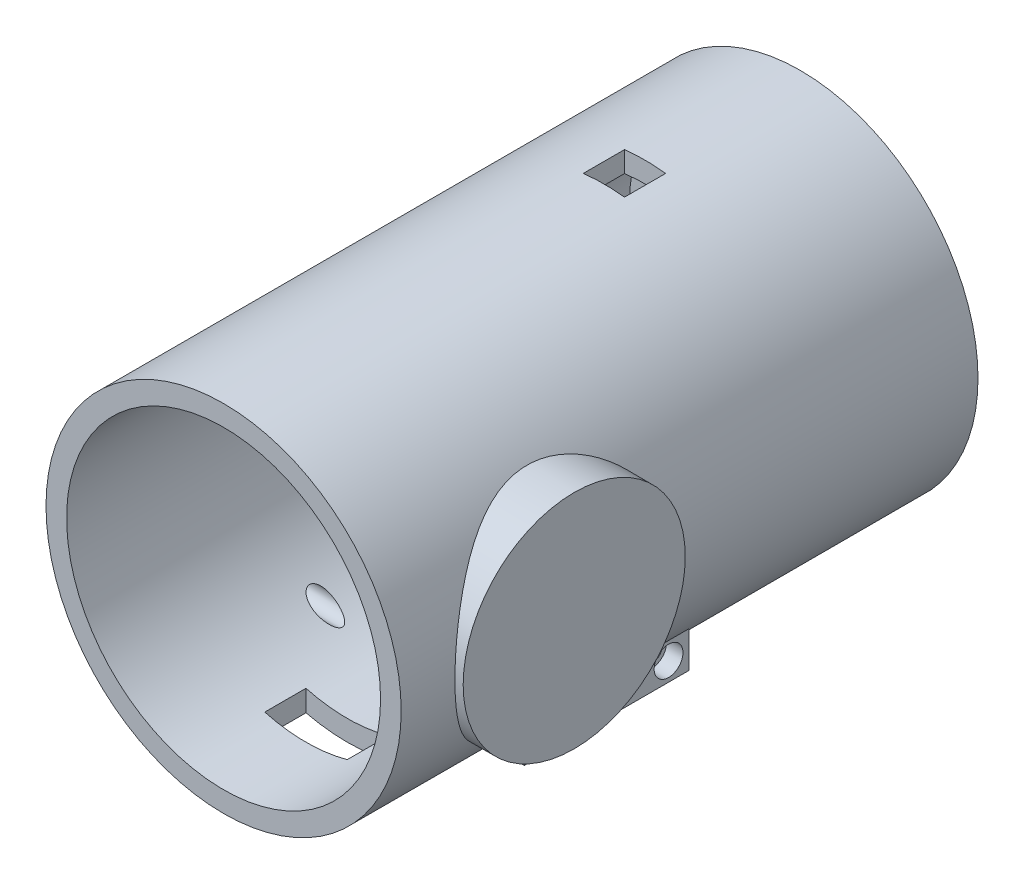
SolidWorks part; units mm, degrees
other "Markup1"
sketch "Sketch14" plane through (-43.1, 43.1, 140) normal (-0.1765, 0.0048, 0.9843) x (0.9842, -0.0149, 0.1765)
other "Markup2"
sketch "Sketch23" plane through (45.1, -43.1, 140) normal (0.9491, -0.0629, 0.3087) x (0.311, 0.031, -0.9499)
ref_plane "Front Plane" through (0, 0, 0) normal (0, 0, 1) x (1, 0, 0)
ref_plane "Top Plane" through (0, 0, 0) normal (0, 1, 0) x (1, 0, 0)
ref_plane "Right Plane" through (0, 0, 0) normal (1, 0, 0) x (0, 0, -1)
sketch "Sketch1" plane through (0, 0, 0) normal (0, 0, 1) x (1, 0, 0)
  circle A1 centre (0, 0) radius 43.1
  dimension "D1" = 86.2
extrude "Main Body" add sketch "Sketch1" along normal blind 140
ref_plane "Plane1" through (0, 43.1, 0) normal (0, 1, 0) x (1, 0, 0)
sketch "Sketch6" plane through (0, 43.1, 0) normal (0, 1, 0) x (1, 0, 0)
  line L2 (-5, -47.7) -> (5, -47.7)
  line L3 (-5, -47.7) -> (-5, -37.7)
  line L4 (-5, -37.7) -> (5, -37.7)
  line L5 (5, -47.7) -> (5, -37.7)
  line L6 (-5, -47.7) -> (5, -37.7) construction
  line L7 (-5, -37.7) -> (5, -47.7) construction
  point P2 (0, -42.7)
  dimension "D2" = 10
  dimension "D1" = 42.7
  dimension "D3" = 10
extrude "Cut-Extrude3" cut sketch "Sketch6" against normal through all
ref_plane "Plane2" through (45.1, 0, 0) normal (1, 0, 0) x (0, 0, -1)
sketch "Sketch8" plane through (45.1, 0, 0) normal (1, 0, 0) x (0, 0, -1)
  circle A0 centre (-100, 0) radius 26.95
  dimension "D1" = 53.9
  dimension "D2" = 100
extrude "Boss-Extrude2" add sketch "Sketch8" against normal blind 20
mirror "Mirror1" [suppressed] about plane through (0, 0, 0) normal (1, 0, 0)
sketch "Sketch5" plane through (0, 0, 140) normal (0, 0, 1) x (1, 0, 0)
  circle A0 centre (0, 0) radius 31.75
  dimension "D1" = 63.5
extrude "Hole 1" cut sketch "Sketch5" against normal through all
sketch "Sketch10" plane through (0, 0, 0) normal (0, 1, 0) x (1, 0, 0)
  line L0 (43.1, 0) -> (-43.1, 0) construction
  line L1 (-10, -120) -> (10, -120)
  line L2 (-10, -120) -> (-10, -110)
  line L3 (-10, -110) -> (10, -110)
  line L4 (10, -120) -> (10, -110)
  line L5 (-10, -120) -> (10, -110) construction
  line L6 (-10, -110) -> (10, -120) construction
  point P0 (0, -115)
  point P7 (-10, -115)
  dimension "D1" = 110
  dimension "D2" = 10
  dimension "D3" = 20
extrude "Motor Wire Hole" cut sketch "Sketch10" against normal through all
sketch "Sketch27" plane through (0, 0, 0) normal (1, 0, 0) x (0, 0, -1)
  line L1 (-100, -36.5) -> (-60, -36.5)
  line L2 (-100, -36.5) -> (-100, -27.5)
  line L3 (-100, -27.5) -> (-60, -27.5)
  line L4 (-60, -36.5) -> (-60, -27.5)
  dimension "D1" = 60
  dimension "D2" = 27.5
  dimension "D3" = 40
  dimension "D4" = 9
extrude "Boss-Extrude9" add sketch "Sketch27" along normal blind 33 and the other way blind 33
sketch "Sketch11" plane through (0, 0, 0) normal (1, 0, 0) x (0, 0, -1)
  circle A0 centre (-65, -32) radius 2.5
  circle A1 centre (-95, -32) radius 2.5
  dimension "D3" = 5
  dimension "D1" = 65
  dimension "D2" = 32
  dimension "D4" = 30
extrude "Cut-Extrude6" cut sketch "Sketch11" against normal through all both and the other way through all
sketch "Sketch28" plane through (-33, 0, 0) normal (-1, 0, 0) x (0, 0, 1)
  line L0 (62.9793, -28.5) -> (67.0207, -28.5)
  line L1 (67.0207, -28.5) -> (69.0415, -32)
  line L2 (69.0415, -32) -> (67.0207, -35.5)
  line L3 (67.0207, -35.5) -> (62.9793, -35.5)
  line L4 (62.9793, -35.5) -> (60.9585, -32)
  line L6 (60.9585, -32) -> (62.9793, -28.5)
  line L7 (92.9793, -28.5) -> (97.0207, -28.5)
  line L8 (97.0207, -28.5) -> (99.0415, -32)
  line L9 (99.0415, -32) -> (97.0207, -35.5)
  line L10 (97.0207, -35.5) -> (92.9793, -35.5)
  line L11 (92.9793, -35.5) -> (90.9585, -32)
  line L12 (90.9585, -32) -> (92.9793, -28.5)
  circle A0 centre (65, -32) radius 3.5 construction
  circle A1 centre (65, -32) radius 2.5 construction
  circle A2 centre (95, -32) radius 3.5 construction
  circle A3 centre (95, -32) radius 2.5 construction
  dimension "D1" = 7
  dimension "D2" = 7
extrude "Cut-Extrude7" cut sketch "Sketch28" against normal blind 3
sketch "Sketch29" plane through (33, 0, 0) normal (1, 0, 0) x (0, 0, -1)
  circle A0 centre (-95, -32) radius 3.5
  circle A1 centre (-65, -32) radius 3.5
  dimension "D1" = 7
extrude "Cut-Extrude8" cut sketch "Sketch29" against normal blind 4
sketch "Sketch2" plane through (0, 0, 140) normal (0, 0, 1) x (1, 0, 0)
  circle A0 centre (0, 0) radius 38.1
  dimension "D1" = 76.2
extrude "Cut-Extrude5" cut sketch "Sketch2" against normal blind 135
sketch "Sketch9" plane through (0, 0, 5) normal (0, 0, 1) x (1, 0, 0)
  circle A0 centre (0, 0) radius 38.1
  circle A1 centre (0, 0) radius 36.44
  dimension "D1" = 76.2
  dimension "D2" = 1.66
extrude "Boss-Extrude3" add sketch "Sketch9" along normal blind 10
